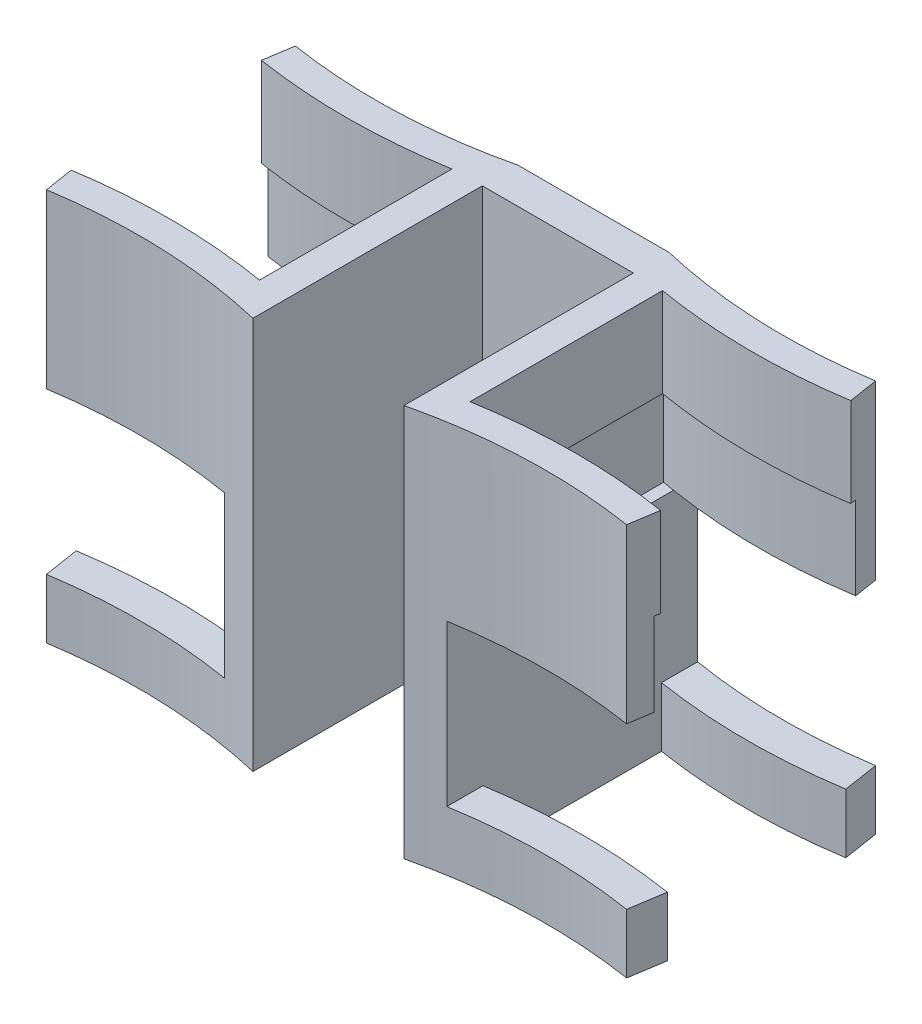
SolidWorks part; units mm, degrees
ref_plane "Front Plane" through (0, 0, 0) normal (0, 0, 1) x (1, 0, 0)
ref_plane "Top Plane" through (0, 0, 0) normal (0, 1, 0) x (1, 0, 0)
ref_plane "Right Plane" through (0, 0, 0) normal (1, 0, 0) x (0, 0, -1)
sketch "Sketch1" plane through (0, 0, 0) normal (0, 1, 0) x (1, 0, 0)
  line L0 (-6, -1.2833) -> (-6, -31.2833)
  line L1 (0, 0) -> (0, -38.5665)
  line L2 (-37, -1.2833) -> (-36.07, 4.6442)
  line L3 (-37, -31.2833) -> (-36.07, -37.2107)
  line L4 (0, 6) -> (25.4, 6)
  line L5 (31.4, -1.2833) -> (31.4, -31.2833)
  line L6 (25.4, 0) -> (25.4, -38.5665)
  line L7 (62.4, -1.2833) -> (61.47, 4.6442)
  line L8 (62.4, -31.2833) -> (61.47, -37.2107)
  line L9 (0, 0) -> (25.4, 0)
  line L10 (0, 6) -> (0, -38.5665) construction
  line L11 (25.4, 6) -> (25.4, -38.5665) construction
  arc A0 (-6, -1.2833) -> (-37, -1.2833) centre (-21.5, 97.5082) cw
  arc A1 (-6, -31.2833) -> (-37, -31.2833) centre (-21.5, -130.0747) ccw
  arc A2 (0, 6) -> (-36.07, 4.6442) centre (-21.5, 97.5082) cw
  arc A3 (0, -38.5665) -> (-36.07, -37.2107) centre (-21.5, -130.0747) ccw
  arc A4 (31.4, -1.2833) -> (62.4, -1.2833) centre (46.9, 97.5082) ccw
  arc A5 (31.4, -31.2833) -> (62.4, -31.2833) centre (46.9, -130.0747) cw
  arc A6 (25.4, 6) -> (61.47, 4.6442) centre (46.9, 97.5082) ccw
  arc A7 (25.4, -38.5665) -> (61.47, -37.2107) centre (46.9, -130.0747) cw
  point P20 (0, 0)
  dimension "D1" = 100
  dimension "D2" = 31
  dimension "D3" = 30
  dimension "D4" = 31
  dimension "D5" = 31
  dimension "D7" = 31
  dimension "D9" = 30
  dimension "D10" = 25.4
  dimension "D11" = 6
  dimension "D6" = 6
  dimension "D8" = 6
extrude "Boss-Extrude1" add sketch "Sketch1" along normal blind 66
sketch "Sketch2" plane through (0, 66, 0) normal (0, 1, 0) x (1, 0, 0)
  line L12 (-6, -1.2833) -> (-6, -31.2833)
  line L13 (31.4, -1.2833) -> (31.4, -31.2833)
  line L14 (62.4, -1.2833) -> (62.4, -31.2833)
  line L15 (-37, -1.2833) -> (-37, -31.2833)
  line L16 (-5, -0.1071) -> (-5, -32.4594)
  line L17 (-38, -0.1071) -> (-38, -32.4594)
  line L18 (63.4, -0.1071) -> (63.4, -32.4594)
  line L19 (30.4, -0.1071) -> (30.4, -32.4594)
  arc A24 (-37, -1.2833) -> (-6, -1.2833) centre (-21.5, 97.5082) ccw
  arc A25 (-37, -31.2833) -> (-6, -31.2833) centre (-21.5, -130.0747) cw
  arc A26 (31.4, -1.2833) -> (62.4, -1.2833) centre (46.9, 97.5082) ccw
  arc A27 (31.4, -31.2833) -> (62.4, -31.2833) centre (46.9, -130.0747) cw
  arc A28 (62.4, -31.2833) -> (31.4, -31.2833) centre (46.9, -130.0747) ccw construction
  arc A29 (-38, -0.1071) -> (-5, -0.1071) centre (-21.5, 97.5082) ccw
  arc A30 (-38, -32.4594) -> (-5, -32.4594) centre (-21.5, -130.0747) cw
  arc A31 (30.4, -32.4594) -> (63.4, -32.4594) centre (46.9, -130.0747) cw
  arc A32 (30.4, -0.1071) -> (63.4, -0.1071) centre (46.9, 97.5082) ccw
  dimension "D1" = 100
  dimension "D2" = 1
  dimension "D3" = 1
extrude "Cut-Extrude1" cut sketch "Sketch2" against normal blind 15
sketch "Sketch3" plane through (0, 51, 0) normal (0, 1, 0) x (1, 0, 0)
  line L0 (-37, -1.2833) -> (-37, -31.2833)
  line L1 (-6, -1.2833) -> (-6, -31.2833)
  line L2 (31.4, -1.2833) -> (31.4, -31.2833)
  line L3 (62.4, -1.2833) -> (62.4, -31.2833)
  line L4 (-4, 1.0834) -> (-4, -33.6499)
  line L5 (-39, 1.0834) -> (-39, -33.6499)
  line L6 (64.4, 1.0834) -> (64.4, -33.6499)
  line L7 (29.4, 1.0834) -> (29.4, -33.6499)
  arc A0 (-37, -1.2833) -> (-6, -1.2833) centre (-21.5, 97.5082) ccw
  arc A1 (-37, -31.2833) -> (-6, -31.2833) centre (-21.5, -130.0747) cw
  arc A2 (31.4, -1.2833) -> (62.4, -1.2833) centre (46.9, 97.5082) ccw
  arc A3 (31.4, -31.2833) -> (62.4, -31.2833) centre (46.9, -130.0747) cw
  arc A4 (-39, -33.6499) -> (-4, -33.6499) centre (-21.5, -130.0747) cw
  arc A5 (-39, 1.0834) -> (-4, 1.0834) centre (-21.5, 97.5082) ccw
  arc A6 (29.4, -33.6499) -> (64.4, -33.6499) centre (46.9, -130.0747) cw
  arc A7 (29.4, 1.0834) -> (64.4, 1.0834) centre (46.9, 97.5082) ccw
  dimension "D1" = 100
  dimension "D2" = 2
extrude "Cut-Extrude2" cut sketch "Sketch3" against normal blind 14
sketch "Sketch4" plane through (-6, 0, 0) normal (-1, 0, 0) x (0, 0, 1)
  line L0 (-6, 37) -> (38.5665, 37)
  line L1 (31.2833, 37) -> (1.2833, 37) construction
  line L2 (38.5665, 37) -> (38.5665, 10)
  line L3 (38.5665, 10) -> (-6, 10)
  line L4 (-6, 10) -> (-6, 37)
  line L5 (-6, 66) -> (-6, 0) construction
  line L6 (38.5665, 66) -> (38.5665, 0) construction
  line L7 (1.2833, 0) -> (31.2833, 0) construction
  dimension "D1" = 10
extrude "Cut-Extrude3" cut sketch "Sketch4" along normal through all
sketch "Sketch5" plane through (31.4, 0, 0) normal (1, 0, 0) x (0, 0, -1)
  line L0 (-38.5665, 37) -> (6, 37)
  line L1 (6, 37) -> (6, 10)
  line L2 (6, 10) -> (-38.5665, 10)
  line L3 (-38.5665, 10) -> (-38.5665, 37)
  line L4 (-1.2833, 37) -> (-31.2833, 37) construction
  line L5 (-38.5665, 66) -> (-38.5665, 0) construction
  line L6 (6, 66) -> (6, 0) construction
  line L7 (-31.2833, 0) -> (-1.2833, 0) construction
  dimension "D1" = 10
extrude "Cut-Extrude4" cut sketch "Sketch5" along normal through all
